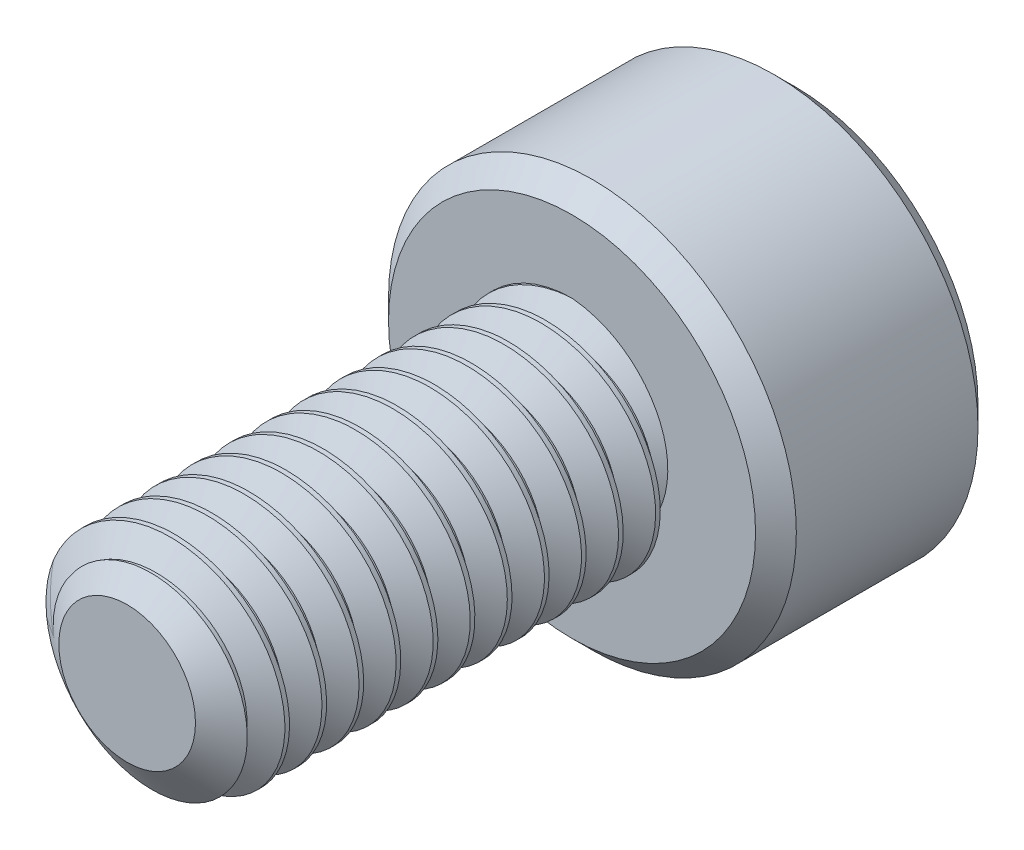
SolidWorks part; units mm, degrees
other "DetailItem1"
ref_plane "Front Plane" through (0, 0, 0) normal (0, 0, 1) x (1, 0, 0)
ref_plane "Top Plane" through (0, 0, 0) normal (0, 1, 0) x (1, 0, 0)
ref_plane "Right Plane" through (0, 0, 0) normal (1, 0, 0) x (0, 0, -1)
sketch "Sketch1" plane through (0, 0, 0) normal (0, 0, 1) x (1, 0, 0)
  circle A0 centre (0, 0) radius 1.5
  dimension "OD" = 3
extrude "Extrude1" add sketch "Sketch1" against normal blind 6
sketch "Sketch2" plane through (0, 0, 0) normal (0, 0, 1) x (1, 0, 0)
  circle A0 centre (0, 0) radius 1.5 construction
  circle A1 centre (0, 0) radius 1.5
curve "Helix/Spiral1" pitch 0.5 height 6.5 radius 1.5 centre (0, 0, 0) axis (0, 0, -1) start towards (0, 1, 0) parameters "pitch"=0.5
sketch "Sketch3" plane through (0, 0, 0) normal (1, 0, 0) x (0, 0, -1)
  line L0 (-0.4375, 1.5) -> (-0.25, 1.1752)
  line L1 (-0.25, 1.1752) -> (-0.1875, 1.1752)
  line L2 (-0.1875, 1.1752) -> (0, 1.5)
  line L3 (-0.4375, 1.5) -> (0, 1.5)
  line L4 (-0.2187, 1.5) -> (-0.2188, 1.1752) construction
  line L5 (-0.3438, 1.3376) -> (-0.0938, 1.3376) construction
  line L6 (0, 1.5) -> (0, -1.5) construction
  dimension "D1" = 0.0625
  dimension "D2" = 0.25
  dimension "D3" = 60
sweep "Cut-Sweep1" cut profiles "Sketch3" path "Helix/Spiral1"
sketch "Sketch4" plane through (0, 0, 0) normal (1, 0, 0) x (0, 0, -1)
  line L0 (0.4053, 1.5) -> (0, 0.9212)
  line L1 (0, 0.9212) -> (0, 1.5)
  line L2 (0.4053, 1.5) -> (0, 1.5)
  line L3 (-0.4375, 1.5) -> (0, 1.5) construction
  line L4 (0, 0) -> (7.0209, 0) construction
  dimension "D1" = 55
  dimension "D2" = 0.254
revolve "Cut-Revolve1" cut sketch "Sketch4" angle 360 about L4
sketch "Sketch6" plane through (0, 0, -6) normal (0, 0, -1) x (-1, 0, 0)
  circle A0 centre (0, 0) radius 2.75
  dimension "head dia" = 5.5
extrude "Extrude2" add sketch "Sketch6" along normal blind 3
sketch "Sketch7" plane through (0, 0, -9) normal (0, 0, -1) x (-1, 0, 0)
  line L1 (0, 1.4434) -> (-1.25, 0.7217)
  line L2 (-1.25, 0.7217) -> (-1.25, -0.7217)
  line L3 (-1.25, -0.7217) -> (0, -1.4434)
  line L4 (0, -1.4434) -> (1.25, -0.7217)
  line L5 (1.25, -0.7217) -> (1.25, 0.7217)
  line L6 (1.25, 0.7217) -> (0, 1.4434)
  circle A0 centre (0, 0) radius 1.25 construction
  dimension "hex dia" = 2.5
extrude "Cut-Extrude1" cut sketch "Sketch7" against normal blind 1.875
sketch "Sketch8" plane through (0, 0, -9) normal (0, 0, -1) x (-1, 0, 0)
  circle A0 centre (0, 0) radius 1.4434
extrude "Cut-Extrude2" cut sketch "Sketch8" against normal through all draft 45
chamfer "Chamfer1" distance 0.275 angle 45 2 edges at (-2.75, 0, -9) (-2.75, 0, -6)
sketch "Sketch10" plane through (0, 0, -6) normal (0, 0, 1) x (1, 0, 0)
  circle A1 centre (0, 0) radius 1.5
  circle A2 centre (0, 0) radius 1.5
  dimension "D1" = 0
ref_plane "Plane1" through (0, 0, 0) normal (0, 0, 1) x (1, 0, 0)
extrude "partial thread" [suppressed] add sketch "Sketch10" along normal up to surface (4 mm away) separate body up to plane "Plane1"
chamfer "Chamfer2" [suppressed] distance 0.06 angle 45
combine bodies "Combine1" [suppressed] operation type add bodies to combine 107 108
sketch "Sketch9" plane through (0, 0, 0) normal (1, 0, 0) x (0, 0, -1)
  line L0 (0, 1.5) -> (0, -1.5) construction
  line L1 (1.25, 1.5) -> (1.25, -1.5) construction
  dimension "D1" = 1.25
  dimension "D4" = 0.635
  dimension "D5" = 0.3302
equation "\"D3@Helix/Spiral1\" = \"screw length@Extrude1\"+\"pitch@Helix/Spiral1\""
equation "\"D1@Sketch3\" = \"pitch@Helix/Spiral1\"*.125"
equation "\"D2@Sketch3\" = \"pitch@Helix/Spiral1\"*.5"
equation "\"D1@Cut-Extrude1\" = \"hex dia@Sketch7\"*.75"
equation "\"D1@Chamfer1\" = \"head dia@Sketch6\"*.05"
equation "\"D1@Sketch9\" = \"pitch@Helix/Spiral1\"*2.5"
equation "\"D1@Chamfer2\"=\"OD@Sketch1\"*.02"
